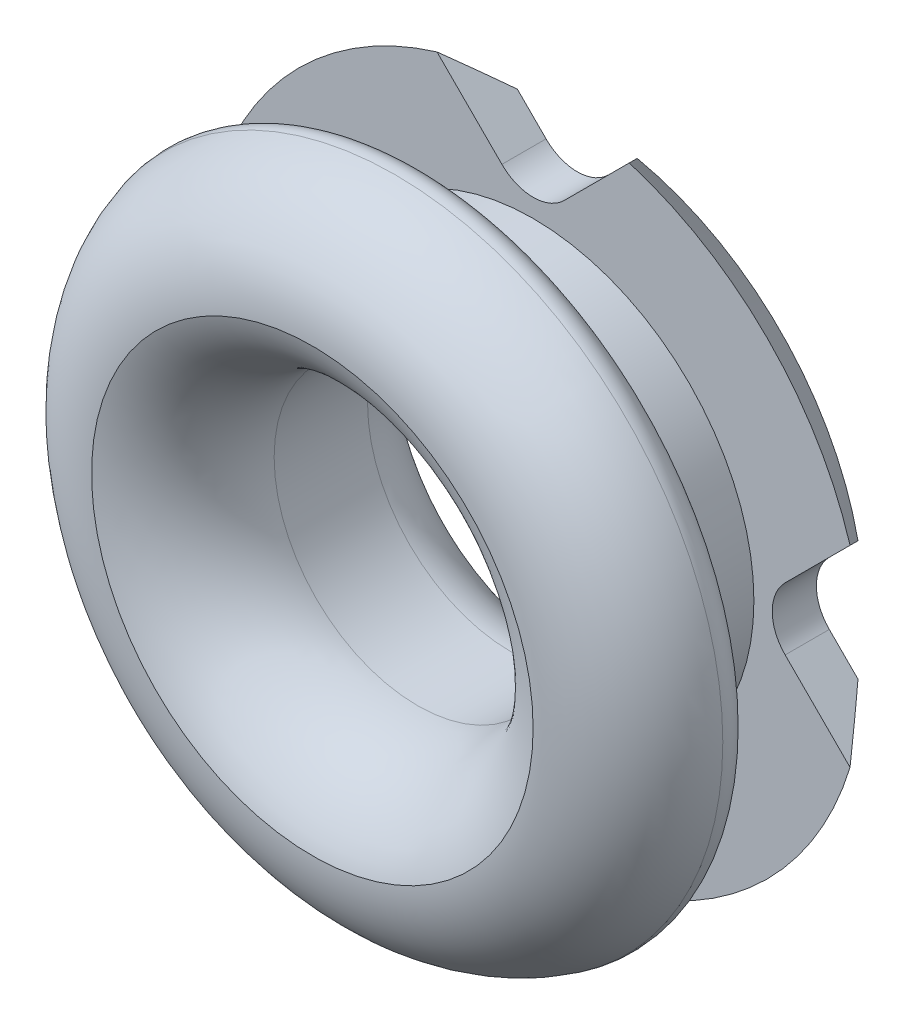
SolidWorks part; units mm, degrees
material "AISI 1035 Steel (SS)"
ref_plane "Front" through (0, 0, 0) normal (0, 0, 1) x (1, 0, 0)
ref_plane "Top" through (0, 0, 0) normal (0, 1, 0) x (1, 0, 0)
ref_plane "Right" through (0, 0, 0) normal (1, 0, 0) x (0, 0, -1)
sketch "Sketch1" plane through (0, 0, 0) normal (0, 0, 1) x (1, 0, 0)
  circle A0 centre (0, 0) radius 1
  circle A1 centre (0, 0) radius 0.65
  dimension "D1" = 2
  dimension "D2" = 1.3
extrude "Boss-Extrude1" add sketch "Sketch1" along normal blind 0.5
sketch "Sketch3" plane through (0, 0, 0.5) normal (0, 0, 1) x (1, 0, 0)
  circle A0 centre (0, 0) radius 1.5
  circle A1 centre (0, 0) radius 0.65
  dimension "D1" = 3
extrude "Boss-Extrude4" add sketch "Sketch3" along normal blind 0.5
sketch "Sketch4" plane through (0, 0, 0) normal (0, 0, -1) x (-1, 0, 0)
  line L0 (0, 1) -> (-0.4354, 1.4354)
  line L1 (0, 1) -> (0.4354, 1.4354)
  line L2 (1, 0) -> (1.4354, 0.4354)
  line L3 (1, 0) -> (1.4354, -0.4354)
  line L4 (0, -1.5) -> (0, 1.5) construction
  line L5 (-1.5, 0) -> (1.5, 0) construction
  line L6 (0, -1) -> (-0.4354, -1.4354)
  line L7 (0, -1) -> (0.4354, -1.4354)
  line L8 (-1, 0) -> (-1.4354, 0.4354)
  line L9 (-1, 0) -> (-1.4354, -0.4354)
  arc A0 (-0.4354, 1.4354) -> (-1.4354, 0.4354) centre (0, 0) ccw
  circle A1 centre (0, 0) radius 0.65
  circle A2 centre (0, 0) radius 1.5 construction
  arc A3 (1.4354, 0.4354) -> (0.4354, 1.4354) centre (0, 0) ccw
  arc A4 (0.4354, -1.4354) -> (1.4354, -0.4354) centre (0, 0) ccw
  arc A5 (-1.4354, -0.4354) -> (-0.4354, -1.4354) centre (0, 0) ccw
  dimension "D1" = 3
  dimension "D2" = 90
  dimension "D3" = 45
  dimension "D4" = 90
  dimension "D5" = 45
  dimension "D7" = 90
  dimension "D8" = 45
  dimension "D9" = 90
  dimension "D10" = 45
extrude "Boss-Extrude5" add sketch "Sketch4" along normal blind 0.2
fillet "Fillet4" radius 0.5 1 edges at (1.5, 0, 1)
fillet "Fillet5" radius 0.5 1 edges at (0.65, 0, 1)
fillet "Fillet6" radius 0.1 1 edges at (1.5, 0, 0.5)
chamfer "Chamfer2" distance 0.2 angle 45 4 edges at (-1.0607, -1.0607, -0.2) (-1.0607, 1.0607, -0.2) (1.0607, 1.0607, -0.2) (1.0607, -1.0607, -0.2)
fillet "Fillet8" radius 0.2 4 edges at (0, 1, -0.1) (1, 0, -0.1) (0, -1, -0.1) (-1, 0, -0.1)
fillet "Fillet9" radius 0.1 1 edges at (-0.9192, -0.9192, -0.2)
fillet "Fillet10" radius 0.3 1 edges at (-0.65, 0, -0.2)
